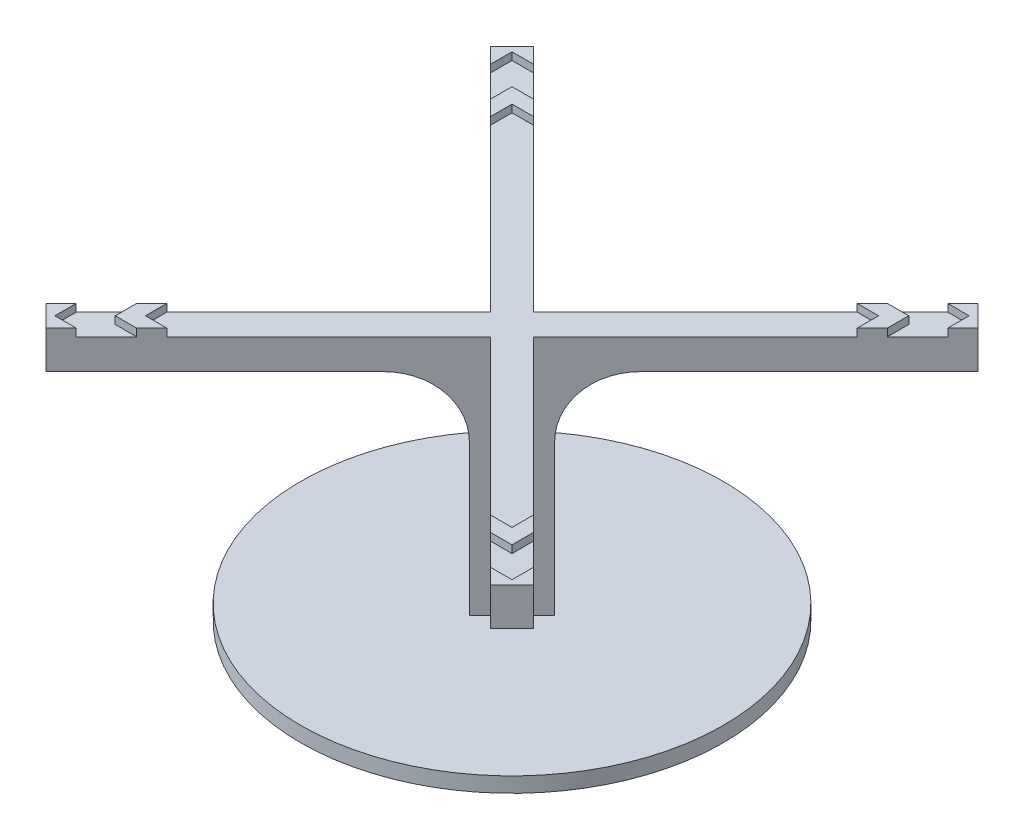
SolidWorks part; units mm, degrees
ref_plane "Front Plane" through (0, 0, 0) normal (0, 0, 1) x (1, 0, 0)
ref_plane "Top Plane" through (0, 0, 0) normal (0, 1, 0) x (1, 0, 0)
ref_plane "Right Plane" through (0, 0, 0) normal (1, 0, 0) x (0, 0, -1)
sketch "Sketch5" plane through (0, 0, 0) normal (0, 1, 0) x (1, 0, 0)
  circle A0 centre (0, 0) radius 146.9526
  dimension "D1" = 293.9051
extrude "Boss-Extrude4" add sketch "Sketch5" along normal mid plane 6.35
sketch "Sketch8" plane through (0, 0, 0) normal (0, 0, 1) x (1, 0, 0)
  line L0 (0, 34.2637) -> (0, -61.9336) construction
sketch "Sketch11" plane through (0, 3.175, 0) normal (0, 1, 0) x (1, 0, 0)
  line L0 (0, 137.9723) -> (0, -128.7054) construction
  line L1 (-137.9723, 0) -> (137.9723, 0) construction
  line L2 (0, 0) -> (103.9112, 103.9112) construction
  circle A0 centre (0, 0) radius 146.9526 construction
  dimension "D1" = 45
sketch "Sketch12" plane through (0, 3.175, 0) normal (0, 1, 0) x (1, 0, 0)
  line L1 (-137.9723, 0) -> (137.9723, 0) construction
  circle A24 centre (89.8026, 0) radius 57.15
  circle A28 centre (0, 0) radius 146.9526 construction
  circle A29 centre (0, -89.8026) radius 57.15
  circle A30 centre (-89.8026, 0) radius 57.15
  circle A31 centre (0, 89.8026) radius 57.15
  point P6 (0, 0)
  point P7 (8.7826, 20.0811)
  point P8 (0, 0)
  point P11 (0, 0)
  point P13 (0, 0)
  point P14 (0, 0)
  point P16 (0, 0)
  point P19 (0, 0)
  point P20 (0, 0)
  dimension "D1" = 114.3
  dimension "D2" = 4
sketch "Sketch15" plane through (0, 3.175, 0) normal (0, 1, 0) x (1, 0, 0)
  line L0 (0, 8.9803) -> (99.324, 108.3042)
  line L1 (0, 137.9723) -> (0, -128.7054) construction
  line L2 (-137.9723, 0) -> (137.9723, 0) construction
  line L3 (8.9803, 0) -> (108.3042, 99.324)
  line L4 (8.9803, 0) -> (0, 0)
  line L5 (0, 0) -> (0, 8.9803)
  circle A0 centre (0, 0) radius 146.9526 construction
  circle A1 centre (0, 89.8026) radius 57.15 construction
  circle A2 centre (89.8026, 0) radius 57.15 construction
  arc A3 (108.3042, 99.324) -> (99.324, 108.3042) centre (0, 0) ccw
  dimension "D1" = 45
extrude "Boss-Extrude9" add sketch "Sketch15" along normal blind 101.6
sketch "Sketch17" plane through (0, 104.775, 0) normal (0, 1, 0) x (1, 0, 0)
  line L0 (13.4704, 4.4901) -> (119.1269, 110.1466)
  line L1 (8.9803, 0) -> (108.3042, 99.324) construction
  line L2 (8.9803, 0) -> (108.3042, 99.324) construction
  line L3 (119.1269, 110.1466) -> (110.1466, 119.1269)
  line L5 (110.1466, 119.1269) -> (4.4901, 13.4704)
  line L6 (99.324, 108.3042) -> (0, 8.9803) construction
  line L7 (4.4901, 13.4704) -> (13.4704, 4.4901)
  dimension "D1" = 6.35
extrude "Cut-Extrude1" cut sketch "Sketch17" along normal offset from surface (88.9 mm away) 12.7 from surface up to face at (43.3411, 104.775, -43.3411) starting at face at (1.7766, 3.175, -1.7766)
sketch "Sketch19" plane through (0, 104.775, 0) normal (0, 1, 0) x (1, 0, 0)
  line L0 (89.8026, 0) -> (89.8026, 137.1536) construction
  line L1 (0, 0) -> (103.9112, 103.9112) construction
  line L4 (57.15, 102.5026) -> (77.1026, 102.5026)
  line L10 (77.1026, 102.5026) -> (102.5026, 102.5026)
  line L11 (102.5026, 77.1026) -> (102.5026, 102.5026)
  line L12 (77.1026, 77.1026) -> (102.5026, 102.5026) construction
  line L13 (77.1026, 102.5026) -> (102.5026, 77.1026) construction
  line L14 (77.1026, 57.15) -> (102.5026, 57.15)
  line L15 (102.5026, 57.15) -> (102.5026, 77.1026)
  line L16 (77.1026, 57.15) -> (77.1026, 77.1026)
  line L17 (57.15, 102.5026) -> (57.15, 77.1026)
  line L18 (57.15, 77.1026) -> (77.1026, 77.1026)
  circle A0 centre (89.8026, 0) radius 57.15 construction
  circle A1 centre (0, 89.8026) radius 57.15 construction
  point P4 (89.8026, 89.8026)
  dimension "D1" = 25.4
  dimension "D2" = 25.4
extrude "Boss-Extrude10" add sketch "Sketch19" against normal blind 6.35
sketch "Sketch20" plane through (0, 104.775, 0) normal (0, 1, 0) x (1, 0, 0)
  line L0 (57.15, 102.5026) -> (102.5026, 102.5026)
  line L1 (0, 0) -> (103.9112, 103.9112) construction
  line L2 (102.5026, 102.5026) -> (102.5026, 57.15)
  line L3 (102.5026, 57.15) -> (96.1526, 57.15)
  line L4 (77.1026, 57.15) -> (102.5026, 57.15) construction
  line L5 (96.1526, 57.15) -> (96.1526, 96.1526)
  line L6 (96.1526, 96.1526) -> (57.15, 96.1526)
  line L7 (57.15, 102.5026) -> (57.15, 77.1026) construction
  line L8 (57.15, 96.1526) -> (57.15, 102.5026)
  line L9 (57.15, 77.1026) -> (77.1026, 77.1026)
  line L10 (77.1026, 77.1026) -> (77.1026, 57.15)
  line L11 (77.1026, 57.15) -> (83.4526, 57.15)
  line L12 (83.4526, 57.15) -> (83.4526, 83.4526)
  line L13 (83.4526, 83.4526) -> (57.15, 83.4526)
  line L14 (57.15, 83.4526) -> (57.15, 77.1026)
  dimension "D1" = 6.35
  dimension "D2" = 6.35
extrude "Boss-Extrude11" add sketch "Sketch20" along normal blind 3.175
fillet "Fillet2" radius 25.4 1 edges at (8.9803, 92.075, -8.9803)
sketch "Sketch24" plane through (0, 107.95, 0) normal (0, 1, 0) x (1, 0, 0)
  line L0 (93.5223, 102.5026) -> (102.5026, 93.5223)
  line L1 (102.5026, 57.15) -> (102.5026, 102.5026) construction
  line L2 (102.5026, 93.5223) -> (102.5026, 102.5026) construction
  line L3 (102.5026, 93.5223) -> (118.6435, 109.6632)
  line L4 (118.6435, 109.6632) -> (109.6632, 118.6435)
  line L5 (109.6632, 118.6435) -> (93.5223, 102.5026)
extrude "Cut-Extrude7" cut sketch "Sketch24" against normal up to surface (15.875 mm away) up to face at (65.4017, 92.075, -65.4017)
sketch "Sketch25" plane through (0, 107.95, 0) normal (0, 1, 0) x (1, 0, 0)
  line L0 (52.5624, 61.5426) -> (93.5223, 102.5026)
  line L1 (68.1223, 77.1026) -> (0, 8.9803) construction
  line L2 (93.5223, 102.5026) -> (70.0446, 125.9803)
  line L3 (70.0446, 125.9803) -> (29.0847, 85.0204)
  line L4 (29.0847, 85.0204) -> (52.5624, 61.5426)
  line L5 (61.5426, 52.5624) -> (102.5026, 93.5223)
  line L6 (8.9803, 0) -> (77.1026, 68.1223) construction
  line L7 (102.5026, 93.5223) -> (124.9977, 71.0272)
  line L8 (124.9977, 71.0272) -> (84.0377, 30.0673)
  line L9 (84.0377, 30.0673) -> (61.5426, 52.5624)
extrude "Cut-Extrude8" cut sketch "Sketch25" against normal up to surface (15.875 mm away) up to face at (62.4766, 92.075, -62.4766)
pattern_circular "CirPattern7" count 4 every 90 about axis through (0, 34.2637, 0) along (0, -1, 0) of "Boss-Extrude9", "Cut-Extrude1", "Boss-Extrude10", "Boss-Extrude11", "Fillet2", "Cut-Extrude7", "Cut-Extrude8"
sketch "Sketch26" plane through (0, 3.175, 0) normal (0, 1, 0) x (1, 0, 0)
  circle A0 centre (0, 0) radius 88.9
  circle A2 centre (0, 0) radius 146.9526
  circle A6 centre (0, 0) radius 146.9526
  dimension "D1" = 177.8
  dimension "D2" = 0
extrude "Cut-Extrude9" cut sketch "Sketch26" against normal up to surface (6.35 mm away) up to face at (0, -3.175, 146.9526)
equation "\"cage spacing\"= 0.5'space between cages"
equation "\"cage diameter\"= 4.5in'cage diameter"
equation "\"cage radius\"= \"cage diameter\" / 2'cage radius"
equation "\"D1@Sketch5\"=2*(2^0.5*(\"cage radius\"+\"cage spacing\"/2)+\"cage radius\")"
equation "\"D1@Sketch12\"=\"cage diameter\""
